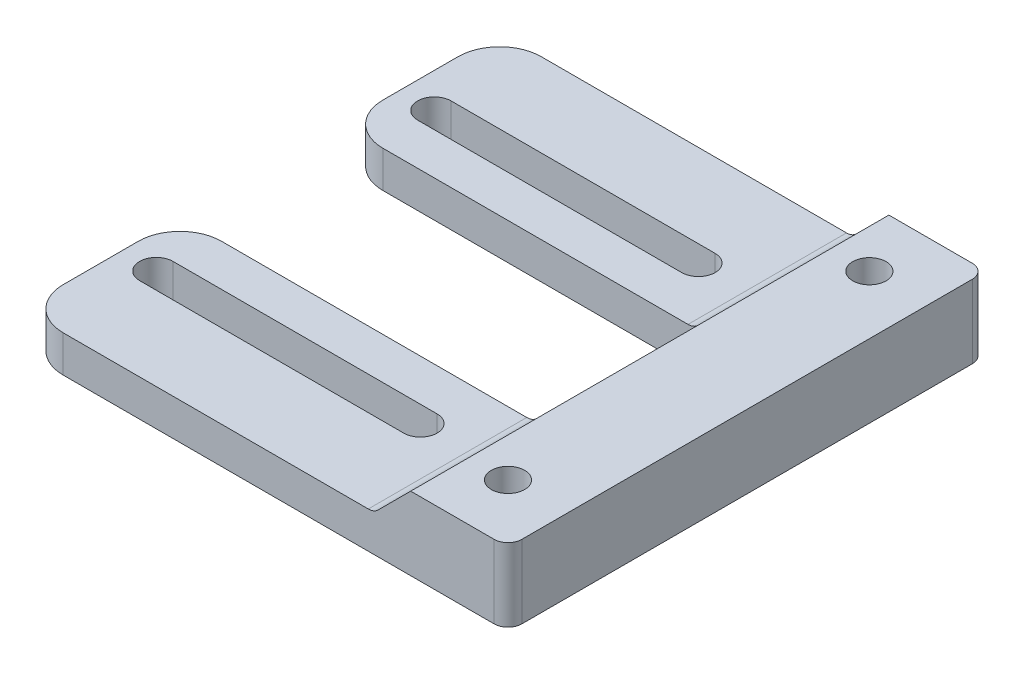
SolidWorks part; units mm, degrees
ref_plane "Front Plane" through (0, 0, 0) normal (0, 0, 1) x (1, 0, 0)
ref_plane "Top Plane" through (0, 0, 0) normal (0, 1, 0) x (1, 0, 0)
ref_plane "Right Plane" through (0, 0, 0) normal (1, 0, 0) x (0, 0, -1)
sketch "Sketch1" plane through (0, 0, 0) normal (0, 0, 1) x (1, 0, 0)
  line L0 (-23, -2.635) -> (-23, -5.27) construction
  line L1 (0, 0) -> (-7, 0)
  line L2 (0, 0) -> (0, -2.635)
  line L3 (0, -2.635) -> (-7, -2.635)
  line L4 (-7, 0) -> (-7, -2.635)
  line L5 (0, -2.635) -> (-35, -2.635)
  line L6 (0, -2.635) -> (0, -5.27)
  line L7 (0, -5.27) -> (-35, -5.27)
  line L8 (-35, -2.635) -> (-35, -5.27)
  line L9 (-32, -2.635) -> (-32, -5.27) construction
  point P13 (-32, -3.9525)
  dimension "D1" = 7
  dimension "D2" = 5.27
  dimension "40" = 35
  dimension "D4" = 16
  dimension "D5" = 9
extrude "Boss-Extrude1" add sketch "Sketch1" along normal mid plane 34.4 contours L5 L8 L7 L6 L3 | L1 L4 L3 L2
sketch "Sketch2" plane through (0, 0, 0) normal (0, 1, 0) x (1, 0, 0)
  circle A0 centre (-4.2, 13) radius 1.2
  circle A1 centre (-4.2, -13) radius 1.2
  point P4 (0, 0)
  dimension "D1" = 2.4
  dimension "D2" = 13
  dimension "D3" = 13
  dimension "D4" = 4.2
extrude "Cut-Extrude1" cut sketch "Sketch2" against normal up to next
sketch "Sketch3" plane through (0, -2.635, 0) normal (0, 1, 0) x (1, 0, 0)
  line L0 (-7, -17.2) -> (-7, 17.2) construction
  line L1 (-35, -5.8) -> (-7, -5.8)
  line L2 (-35, -5.8) -> (-35, 5.8)
  line L3 (-35, 5.8) -> (-7, 5.8)
  line L4 (-7, -5.8) -> (-7, 5.8)
  line L5 (-35, -5.8) -> (-7, 5.8) construction
  line L6 (-35, 5.8) -> (-7, -5.8) construction
  line L7 (-35, -17.2) -> (-35, 17.2) construction
  line L8 (-7, -17.2) -> (-7, 17.2) construction
  line L9 (-32.5, 10) -> (-13.5, 10) construction
  line L10 (-32.5, 11.2) -> (-13.5, 11.2)
  line L11 (-32.5, 8.8) -> (-13.5, 8.8)
  line L12 (-32.5, -10) -> (-13.5, -10) construction
  line L13 (-32.5, -8.8) -> (-13.5, -8.8)
  line L14 (-32.5, -11.2) -> (-13.5, -11.2)
  arc A0 (-32.5, 11.2) -> (-32.5, 8.8) centre (-32.5, 10) ccw
  arc A1 (-13.5, 8.8) -> (-13.5, 11.2) centre (-13.5, 10) ccw
  arc A2 (-32.5, -8.8) -> (-32.5, -11.2) centre (-32.5, -10) ccw
  arc A3 (-13.5, -11.2) -> (-13.5, -8.8) centre (-13.5, -10) ccw
  point P0 (-21, 0)
  point P11 (0, 0)
  point P12 (0, 0)
  point P13 (-23, 10)
  point P21 (-23, -10)
  point P26 (0, 0)
  point P27 (-19, -10.0289)
  point P28 (0, 0)
  point P29 (0, 0)
  point P30 (0, 0)
  point P31 (0, 0)
  point P32 (-21.4043, 10)
  dimension "D3" = 1.2
  dimension "D2" = 19
  dimension "D4" = 20
  dimension "D5" = 10
  dimension "D1" = 3
  dimension "D6" = 16
extrude "Cut-Extrude2" cut sketch "Sketch3" against normal up to next
chamfer "Chamfer1" distance 2.635 1 edges at (-7, -2.635, 11.5)
fillet "Fillet2" radius 1 4 edges at (-7, -2.635, -5.8) (-7, -2.635, 5.8) (-9.635, -2.635, 11.5) (-9.635, -2.635, -11.5)
fillet "Fillet3" radius 3 3 edges at (-35, -3.9525, 5.8) (-35, -3.9525, 17.2) (-35, -3.9525, -5.8)
fillet "Fillet4" radius 1 2 edges at (0, -2.635, -17.2) (0, -2.635, 17.2)
equation "\"D3@Sketch2\"=\"D2@Sketch2\""
equation "\"D5@Sketch3\"=\"D4@Sketch3\"/2"
